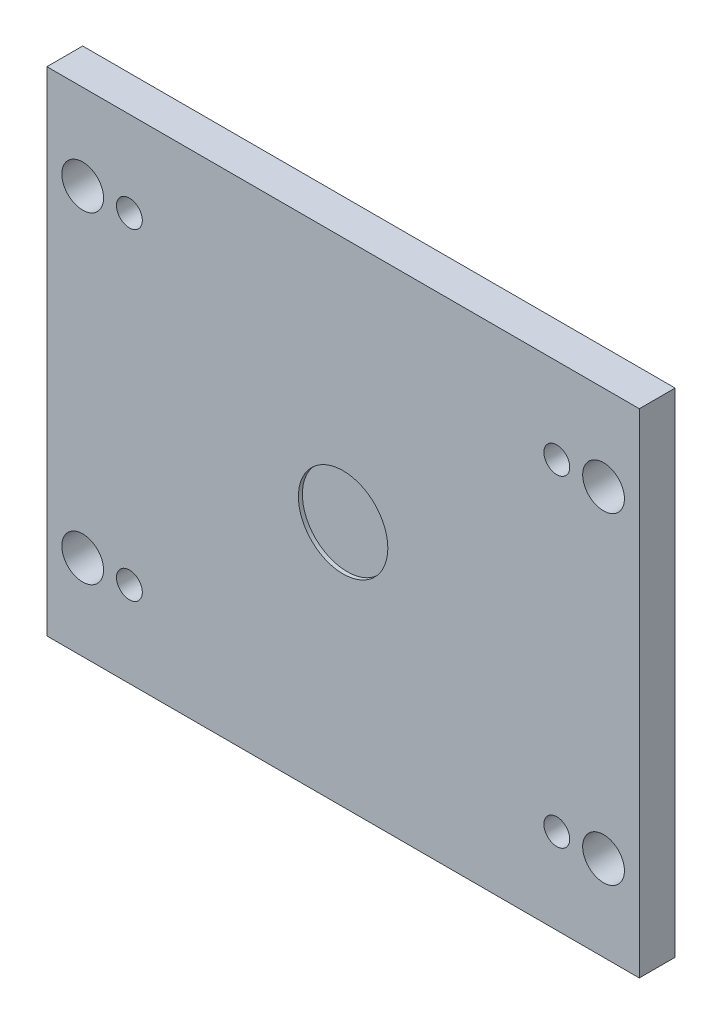
SolidWorks part; units mm, degrees
ref_plane "Płaszczyzna przednia" through (0, 0, 0) normal (0, 0, 1) x (1, 0, 0)
ref_plane "Płaszczyzna górna" through (0, 0, 0) normal (0, 1, 0) x (1, 0, 0)
ref_plane "Płaszczyzna prawa" through (0, 0, 0) normal (1, 0, 0) x (0, 0, -1)
sketch "Szkic1" plane through (0, 0, 0) normal (0, 0, 1) x (1, 0, 0)
  line L0 (-298, -248) -> (298, -248)
  line L1 (298, -248) -> (298, 248)
  line L2 (298, 248) -> (-298, 248)
  line L3 (-298, 248) -> (-298, -248)
extrude "Dodanie-wyciągnięcie1" add sketch "Szkic1" along normal blind 36
ref_plane "Płaszczyzna1" through (0, 0, 36) normal (0, 0, 1) x (1, 0, 0)
sketch "Szkic2" plane through (0, 0, 36) normal (0, 0, 1) x (1, 0, 0)
  circle A0 centre (0, 0) radius 45
extrude "Wytnij-wyciągnięcie1" cut sketch "Szkic2" against normal blind 4
sketch "Szkic3" plane through (0, 0, 36) normal (0, 0, 1) x (1, 0, 0)
  circle A0 centre (262, 162) radius 21
extrude "Wytnij-wyciągnięcie2" cut sketch "Szkic3" against normal blind 36
sketch "Szkic4" plane through (0, 0, 36) normal (0, 0, 1) x (1, 0, 0)
  circle A0 centre (262, -162) radius 21
extrude "Wytnij-wyciągnięcie3" cut sketch "Szkic4" against normal blind 36
sketch "Szkic5" plane through (0, 0, 36) normal (0, 0, 1) x (1, 0, 0)
  circle A0 centre (-262, -162) radius 21
extrude "Wytnij-wyciągnięcie4" cut sketch "Szkic5" against normal blind 36
sketch "Szkic6" plane through (0, 0, 36) normal (0, 0, 1) x (1, 0, 0)
  circle A0 centre (-262, 162) radius 21
extrude "Wytnij-wyciągnięcie5" cut sketch "Szkic6" against normal blind 36
ref_plane "Płaszczyzna2" through (215, 0, 0) normal (1, 0, 0) x (0, 0, -1)
sketch "Szkic7" plane through (215, 0, 0) normal (1, 0, 0) x (0, 0, -1)
  line L0 (-15, 162) -> (-15, 171)
  line L1 (-15, 171) -> (0, 171)
  line L2 (0, 171) -> (0, 162)
  line L3 (0, 162) -> (-15, 162)
  line L4 (0, 162) -> (-15, 162) construction
revolve "Wycięcie-obrót1" cut sketch "Szkic7" angle 360 about L4 reverse direction yes
sketch "Szkic8" plane through (215, 0, 0) normal (1, 0, 0) x (0, 0, -1)
  line L0 (0, -162) -> (0, -171)
  line L1 (0, -171) -> (-15, -171)
  line L2 (-15, -171) -> (-15, -162)
  line L3 (-15, -162) -> (0, -162)
  line L4 (-15, -162) -> (0, -162) construction
revolve "Wycięcie-obrót2" cut sketch "Szkic8" angle 360 about L4 reverse direction yes
ref_plane "Płaszczyzna3" through (-215, 0, 0) normal (1, 0, 0) x (0, 0, -1)
sketch "Szkic9" plane through (-215, 0, 0) normal (1, 0, 0) x (0, 0, -1)
  line L0 (-15, 162) -> (-15, 171)
  line L1 (-15, 171) -> (0, 171)
  line L2 (0, 171) -> (0, 162)
  line L3 (0, 162) -> (-15, 162)
  line L4 (0, 162) -> (-15, 162) construction
revolve "Wycięcie-obrót3" cut sketch "Szkic9" angle 360 about L4 reverse direction yes
sketch "Szkic10" plane through (-215, 0, 0) normal (1, 0, 0) x (0, 0, -1)
  line L0 (0, -162) -> (0, -171)
  line L1 (0, -171) -> (-15, -171)
  line L2 (-15, -171) -> (-15, -162)
  line L3 (-15, -162) -> (0, -162)
  line L4 (-15, -162) -> (0, -162) construction
revolve "Wycięcie-obrót4" cut sketch "Szkic10" angle 360 about L4 reverse direction yes
sketch "Szkic11" plane through (215, 0, 0) normal (1, 0, 0) x (0, 0, -1)
  line L0 (-36, 162) -> (-36, 175)
  line L1 (-36, 175) -> (-15, 175)
  line L2 (-15, 175) -> (-15, 162)
  line L3 (-15, 162) -> (-36, 162)
  line L4 (-15, 162) -> (-36, 162) construction
revolve "Wycięcie-obrót5" cut sketch "Szkic11" angle 360 about L4 reverse direction yes
sketch "Szkic12" plane through (215, 0, 0) normal (1, 0, 0) x (0, 0, -1)
  line L0 (-15, -162) -> (-15, -175)
  line L1 (-15, -175) -> (-36, -175)
  line L2 (-36, -175) -> (-36, -162)
  line L3 (-36, -162) -> (-15, -162)
  line L4 (-36, -162) -> (-15, -162) construction
revolve "Wycięcie-obrót6" cut sketch "Szkic12" angle 360 about L4 reverse direction yes
sketch "Szkic13" plane through (-215, 0, 0) normal (1, 0, 0) x (0, 0, -1)
  line L0 (-15, -162) -> (-15, -175)
  line L1 (-15, -175) -> (-36, -175)
  line L2 (-36, -175) -> (-36, -162)
  line L3 (-36, -162) -> (-15, -162)
  line L4 (-36, -162) -> (-15, -162) construction
revolve "Wycięcie-obrót7" cut sketch "Szkic13" angle 360 about L4 reverse direction yes
sketch "Szkic14" plane through (-215, 0, 0) normal (1, 0, 0) x (0, 0, -1)
  line L0 (-36, 162) -> (-36, 175)
  line L1 (-36, 175) -> (-15, 175)
  line L2 (-15, 175) -> (-15, 162)
  line L3 (-15, 162) -> (-36, 162)
  line L4 (-15, 162) -> (-36, 162) construction
revolve "Wycięcie-obrót8" cut sketch "Szkic14" angle 360 about L4 reverse direction yes
ref_plane "Płaszczyzna4" through (0, 0, 15) normal (0, 0, 1) x (1, 0, 0)
ref_plane "IP1 XY" through (0, 0, 0) normal (0, 0, 1) x (1, 0, 0)
ref_plane "IP1 XZ" through (0, 0, 0) normal (0, -1, 0) x (-1, 0, 0)
ref_plane "IP1 YZ" through (0, 0, 0) normal (1, 0, 0) x (0, 0, -1)
ref_axis "IP1 X" through (-80.9, 0, 0) along (1, 0, 0)
ref_axis "IP1 Y" through (0, -50, 0) along (0, 1, 0)
ref_axis "IP1 Z" through (0, 0, 80.9) along (0, 0, -1)
sketch3d "IP1"
  point P0 (0, 0, 0)
ref_plane "IP2 XY" through (0, 0, 15) normal (0, 0, 1) x (1, 0, 0)
ref_plane "IP2 XZ" through (0, 162, 0) normal (0, -1, 0) x (-1, 0, 0)
ref_plane "IP2 YZ" through (-215, 0, 0) normal (1, 0, 0) x (0, 0, -1)
ref_axis "IP2 X" through (-80.9, 162, 15) along (1, 0, 0)
ref_axis "IP2 Y" through (-215, -50, 15) along (0, 1, 0)
ref_axis "IP2 Z" through (-215, 162, 80.9) along (0, 0, -1)
sketch3d "IP2"
  point P0 (-215, 162, 15)
ref_plane "IP3 XY" through (0, 0, 15) normal (0, 0, 1) x (1, 0, 0)
ref_plane "IP3 XZ" through (0, 162, 0) normal (0, -1, 0) x (-1, 0, 0)
ref_plane "IP3 YZ" through (215, 0, 0) normal (1, 0, 0) x (0, 0, -1)
ref_axis "IP3 X" through (-80.9, 162, 15) along (1, 0, 0)
ref_axis "IP3 Y" through (215, -50, 15) along (0, 1, 0)
ref_axis "IP3 Z" through (215, 162, 80.9) along (0, 0, -1)
sketch3d "IP3"
  point P0 (215, 162, 15)
ref_plane "IP4 XY" through (0, 0, 15) normal (0, 0, 1) x (1, 0, 0)
ref_plane "IP4 XZ" through (0, -162, 0) normal (0, -1, 0) x (-1, 0, 0)
ref_plane "IP4 YZ" through (215, 0, 0) normal (1, 0, 0) x (0, 0, -1)
ref_axis "IP4 X" through (-80.9, -162, 15) along (1, 0, 0)
ref_axis "IP4 Y" through (215, -50, 15) along (0, 1, 0)
ref_axis "IP4 Z" through (215, -162, 80.9) along (0, 0, -1)
sketch3d "IP4"
  point P0 (215, -162, 15)
ref_plane "IP5 XY" through (0, 0, 15) normal (0, 0, 1) x (1, 0, 0)
ref_plane "IP5 XZ" through (0, -162, 0) normal (0, -1, 0) x (-1, 0, 0)
ref_plane "IP5 YZ" through (-215, 0, 0) normal (1, 0, 0) x (0, 0, -1)
ref_axis "IP5 X" through (-80.9, -162, 15) along (1, 0, 0)
ref_axis "IP5 Y" through (-215, -50, 15) along (0, 1, 0)
ref_axis "IP5 Z" through (-215, -162, 80.9) along (0, 0, -1)
sketch3d "IP5"
  point P0 (-215, -162, 15)
ref_plane "IP6 XY" through (0, 0, 0) normal (0, 0, 1) x (1, 0, 0)
ref_plane "IP6 XZ" through (0, 162, 0) normal (0, -1, 0) x (-1, 0, 0)
ref_plane "IP6 YZ" through (262, 0, 0) normal (1, 0, 0) x (0, 0, -1)
ref_axis "IP6 X" through (-80.9, 162, 0) along (1, 0, 0)
ref_axis "IP6 Y" through (262, -50, 0) along (0, 1, 0)
ref_axis "IP6 Z" through (262, 162, 80.9) along (0, 0, -1)
sketch3d "IP6"
  point P0 (262, 162, 0)
ref_plane "IP7 XY" through (0, 0, 0) normal (0, 0, 1) x (1, 0, 0)
ref_plane "IP7 XZ" through (0, 162, 0) normal (0, -1, 0) x (-1, 0, 0)
ref_plane "IP7 YZ" through (-262, 0, 0) normal (1, 0, 0) x (0, 0, -1)
ref_axis "IP7 X" through (-80.9, 162, 0) along (1, 0, 0)
ref_axis "IP7 Y" through (-262, -50, 0) along (0, 1, 0)
ref_axis "IP7 Z" through (-262, 162, 80.9) along (0, 0, -1)
sketch3d "IP7"
  point P0 (-262, 162, 0)
ref_plane "IP8 XY" through (0, 0, 0) normal (0, 0, 1) x (1, 0, 0)
ref_plane "IP8 XZ" through (0, -162, 0) normal (0, -1, 0) x (-1, 0, 0)
ref_plane "IP8 YZ" through (-262, 0, 0) normal (1, 0, 0) x (0, 0, -1)
ref_axis "IP8 X" through (-80.9, -162, 0) along (1, 0, 0)
ref_axis "IP8 Y" through (-262, -50, 0) along (0, 1, 0)
ref_axis "IP8 Z" through (-262, -162, 80.9) along (0, 0, -1)
sketch3d "IP8"
  point P0 (-262, -162, 0)
ref_plane "IP9 XY" through (0, 0, 0) normal (0, 0, 1) x (1, 0, 0)
ref_plane "IP9 XZ" through (0, -162, 0) normal (0, -1, 0) x (-1, 0, 0)
ref_plane "IP9 YZ" through (262, 0, 0) normal (1, 0, 0) x (0, 0, -1)
ref_axis "IP9 X" through (-80.9, -162, 0) along (1, 0, 0)
ref_axis "IP9 Y" through (262, -50, 0) along (0, 1, 0)
ref_axis "IP9 Z" through (262, -162, 80.9) along (0, 0, -1)
sketch3d "IP9"
  point P0 (262, -162, 0)
